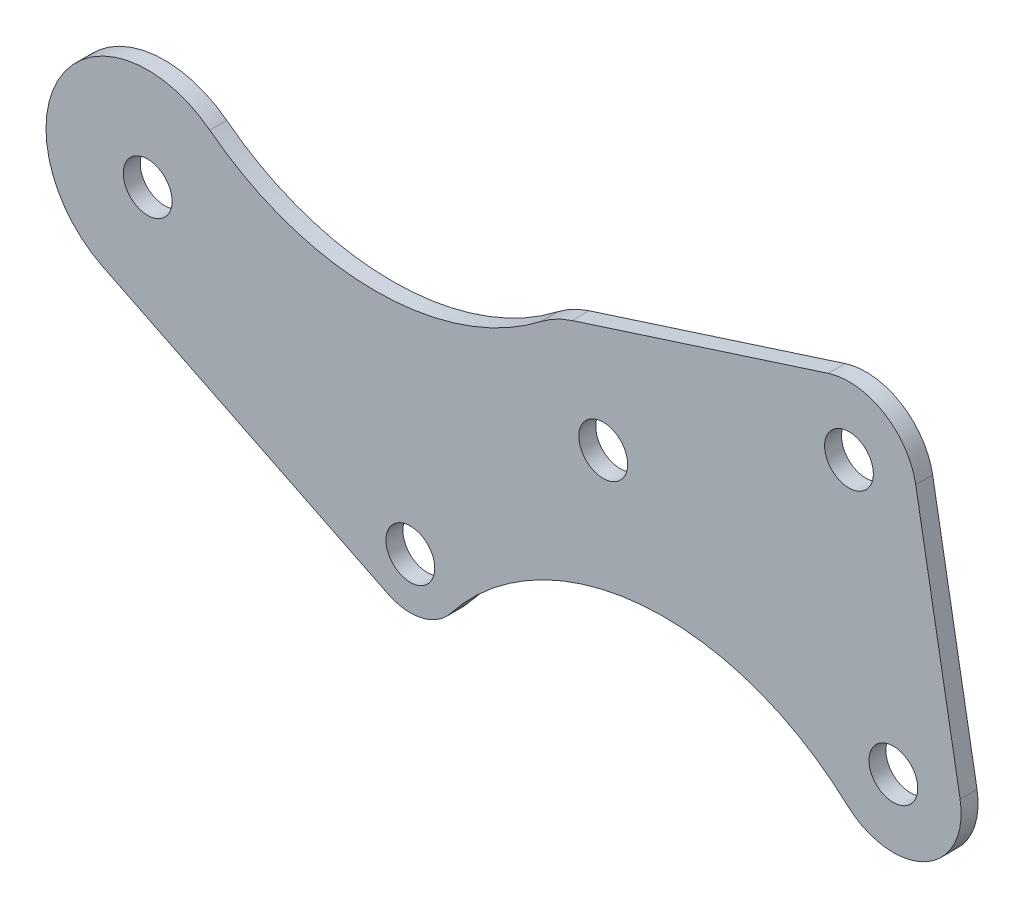
SolidWorks part; units mm, degrees
material "Delrin 2700 NC010, Low Viscosity Acetal Copolymer (SS)"
ref_plane "Front Plane" through (0, 0, 0) normal (0, 0, 1) x (1, 0, 0)
ref_plane "Top Plane" through (0, 0, 0) normal (0, 1, 0) x (1, 0, 0)
ref_plane "Right Plane" through (0, 0, 0) normal (1, 0, 0) x (0, 0, -1)
sketch "Sketch1" plane through (0, 0, 0) normal (0, 0, 1) x (1, 0, 0)
  line L0 (65.6922, 10.7345) -> (42.672, 0) construction
  line L2 (-4.2174, -8.5404) -> (22.4975, -21.7327)
  line L5 (0, 0) -> (42.672, 0) construction
  line L6 (24.6063, -17.4625) -> (24.6062, 0) construction
  line L7 (0, 0) -> (47.7528, 0) construction
  line L9 (76.1024, -11.5907) -> (71.9446, 11.8438)
  line L10 (39.7572, 9.0681) -> (63.749, 16.7799)
  circle A0 centre (0, 0) radius 2.286
  circle A1 centre (42.672, 0) radius 2.286
  circle A2 centre (65.6922, 10.7345) radius 2.286
  circle A3 centre (24.6063, -17.4625) radius 2.286
  arc A4 (5.8189, 7.5409) -> (-4.2174, -8.5404) centre (0, 0) ccw
  arc A5 (22.4975, -21.7327) -> (28.3554, -20.3994) centre (24.6063, -17.4625) ccw
  arc A7 (71.9446, 11.8438) -> (63.749, 16.7799) centre (65.6922, 10.7345) ccw
  circle A8 centre (69.85, -12.7) radius 2.286
  arc A9 (76.1024, -11.5907) -> (65.5501, -17.3726) centre (69.85, -12.7) cw
  arc A10 (28.3554, -20.3994) -> (65.5501, -17.3726) centre (48.3506, -36.0631) cw
  arc A11 (39.7572, 9.0681) -> (36.8531, 7.5409) centre (42.672, 0) ccw
  arc A12 (36.8531, 7.5409) -> (5.8189, 7.5409) centre (21.336, 27.6501) cw
  dimension "D5" = 4.572
  dimension "D6" = 4.572
  dimension "D7" = 155
  dimension "D8" = 9.525
  dimension "D9" = 25.4
  dimension "D10" = 6.35
  dimension "D11" = 4.7625
  dimension "D15" = 6.35
  dimension "D16" = 9.525
  dimension "D17" = 25.4
  dimension "D1" = 42.672
  dimension "D2" = 25.4
  dimension "D3" = 17.4625
  dimension "D4" = 0
  dimension "D12" = 24.6062
  dimension "D13" = 12.7
  dimension "D14" = 69.85
extrude "Boss-Extrude1" add sketch "Sketch1" along normal blind 1.5875
